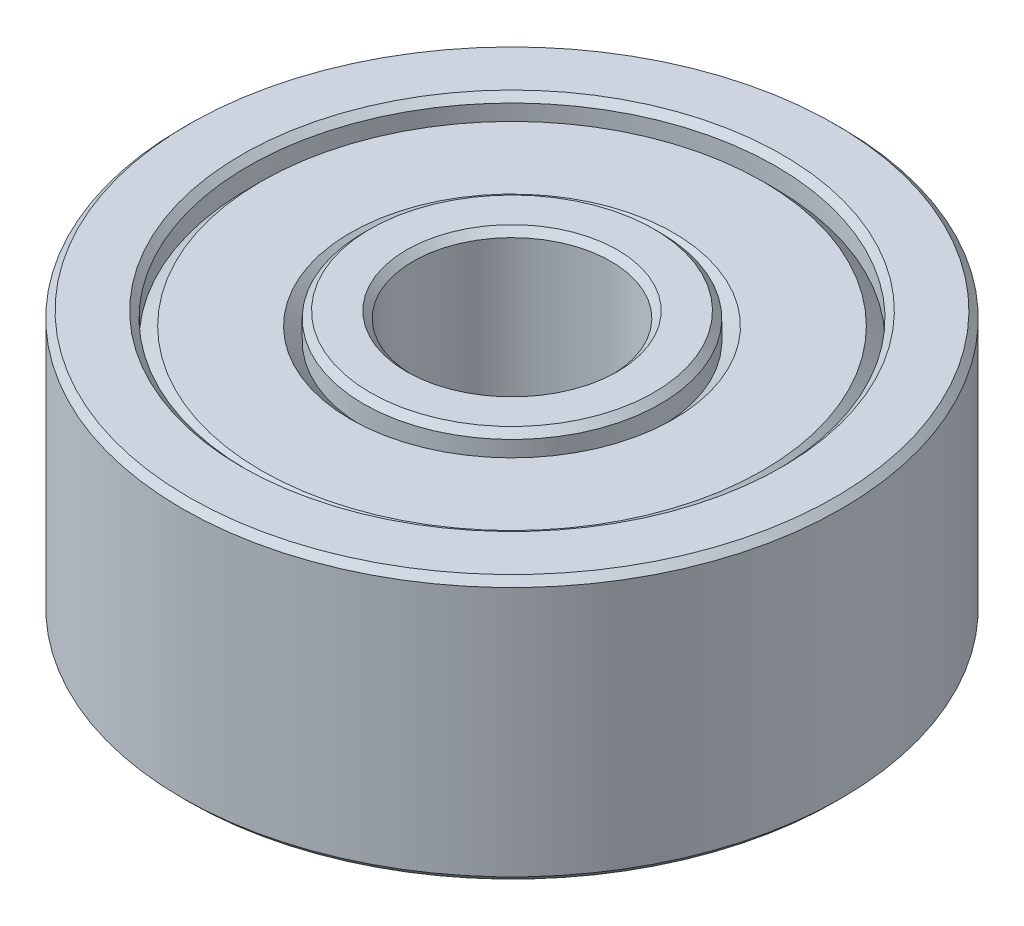
SolidWorks part; units mm, degrees
ref_plane "Front Plane" through (0, 0, 0) normal (0, 0, 1) x (1, 0, 0)
ref_plane "Top Plane" through (0, 0, 0) normal (0, 1, 0) x (1, 0, 0)
ref_plane "Right Plane" through (0, 0, 0) normal (1, 0, 0) x (0, 0, -1)
sketch "Sketch1" plane through (0, 0, 0) normal (1, 0, 0) x (0, 0, -1)
  line L1 (0, 2) -> (5, 2)
  line L2 (0, 2) -> (0, -2) construction
  line L3 (0, -2) -> (5, -2)
  line L4 (5, 2) -> (5, -2)
  line L6 (3.6, 0) -> (0, 0) construction
  line L7 (1.5, 2) -> (1.5, -2)
  dimension "D1" = 4
  dimension "D2" = 5
  dimension "D3" = 1.4
  dimension "D5" = 3
revolve "Revolve1" add sketch "Sketch1" angle 360 about L2 region at (0, 0, -3.25)
sketch "Sketch3" plane through (0, 0, 0) normal (1, 0, 0) x (0, 0, -1)
  line L0 (5, 2) -> (5, -2) construction
  line L1 (1.5, 2) -> (1.5, -2) construction
  line L2 (0, 2) -> (5, 2) construction
  line L3 (5, 2) -> (5, -2) construction
  line L4 (1.5, 2) -> (1.5, -2)
  line L5 (0, 2) -> (5, 2) construction
  line L6 (2.25, 2) -> (4, 2)
  line L7 (2.25, 2) -> (2.25, 1.6)
  line L8 (2.25, 1.6) -> (2.45, 1.8)
  line L9 (2.45, 1.8) -> (3.8, 1.8)
  line L10 (3.8, 1.8) -> (4, 1.6)
  line L11 (4, 1.6) -> (4, 2)
  line L14 (0, 2) -> (0, -2) construction
  line L17 (0, 2) -> (0, -2) construction
  line L18 (2.25, 1.6) -> (4, 1.6) construction
  line L19 (3.125, 1.6) -> (3.125, 2) construction
  dimension "D1" = 1
  dimension "D2" = 0.2
  dimension "D3" = 0.75
  dimension "D4" = 0.2
  dimension "D5" = 0.2
revolve "Cut-Revolve2" cut sketch "Sketch3" angle 360 about L17 region at (0, 1.8829, -3.125)
mirror "Mirror1" about plane through (0, 0, 0) normal (0, 1, 0) of "Cut-Revolve2"
chamfer "Chamfer1" distance 0.1 angle 45 8 edges at (0, -2, 4) (0, 2, 4) (0, -2, 5) (0, 2, 5) (0, -2, 2.25) (0, 2, 2.25) (0, -2, 1.5) (0, 2, 1.5)
